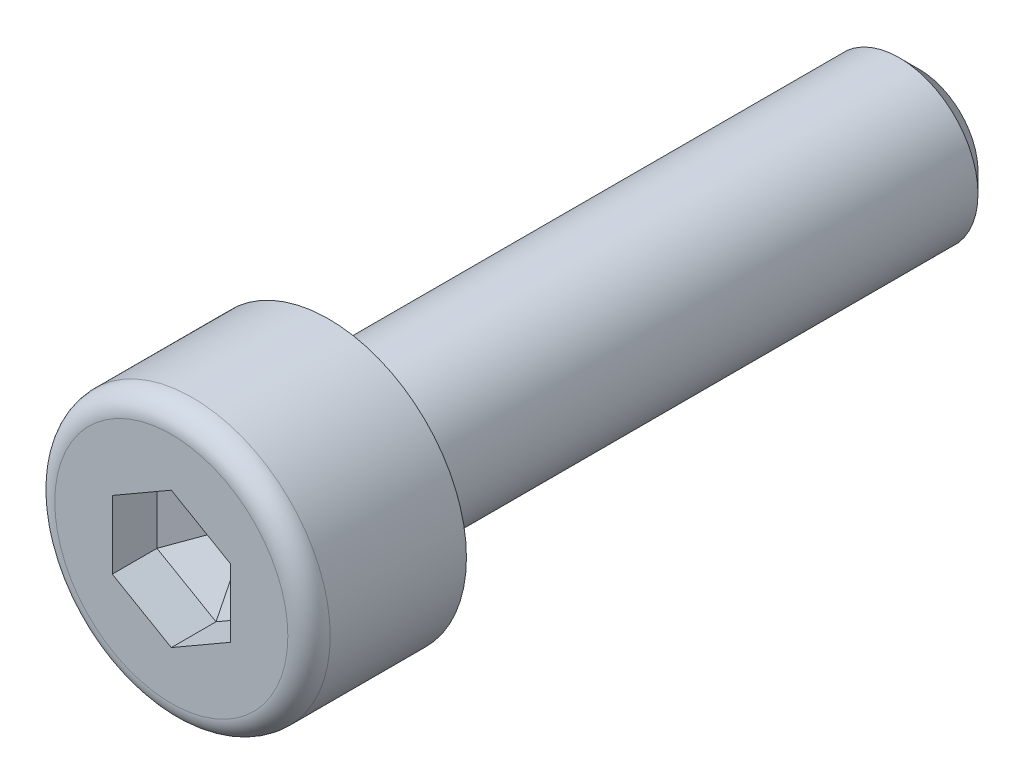
SolidWorks part; units mm, degrees
material "普通碳钢"
ref_plane "前视基准面" through (0, 0, 0) normal (0, 0, 1) x (1, 0, 0)
ref_plane "上视基准面" through (0, 0, 0) normal (0, 1, 0) x (1, 0, 0)
ref_plane "右视基准面" through (0, 0, 0) normal (1, 0, 0) x (0, 0, -1)
sketch "草图1" plane through (0, 0, 0) normal (0, 0, 1) x (1, 0, 0)
  circle A0 centre (0, 0) radius 3.5
  dimension "dk" = 7
extrude "凸台-拉伸1" add sketch "草图1" along normal blind 4
ref_axis "基准轴1" through (0, 0, 4) along (0, 0, -1)
sketch "草图2" plane through (0, 0, 4) normal (0, 0, 1) x (1, 0, 0)
  line L1 (1.5, 0.866) -> (0, 1.7321)
  line L2 (0, 1.7321) -> (-1.5, 0.866)
  line L3 (-1.5, 0.866) -> (-1.5, -0.866)
  line L4 (-1.5, -0.866) -> (0, -1.7321)
  line L5 (0, -1.7321) -> (1.5, -0.866)
  line L6 (1.5, -0.866) -> (1.5, 0.866)
  circle A0 centre (0, 0) radius 1.5 construction
  dimension "s" = 3
extrude "切除-拉伸1" cut sketch "草图2" against normal blind 2
sketch "草图3" plane through (0, 0, 0) normal (0, 0, -1) x (-1, 0, 0)
  circle A0 centre (0, 0) radius 2
  dimension "d" = 4
extrude "凸台-拉伸2" add sketch "草图3" along normal blind 15
cosmetic thread "装饰螺纹线1" parameters "b"=4.9, "D2"=1.221
chamfer "倒角1" distance 0.5 angle 45 1 edges at (-2, 0, -15)
fillet "圆角1" radius 0.5385 1 edges at (3.5, 0, 4)
chamfer "倒角2" distance 0.8646 angle 60 6 edges at (-1.5, 0, 2) (-0.75, 1.299, 2) (0.75, 1.299, 2) (1.5, 0, 2) (-0.75, -1.299, 2) (0.75, -1.299, 2) first distance on face at (-1.5, 0, 3) first distance on face at (-0.75, 1.299, 3) first distance on face at (0.75, 1.299, 3) first distance on face at (1.5, 0, 3) first distance on face at (-0.75, -1.299, 3) first distance on face at (0.75, -1.299, 3)
fillet "圆角2" radius 0.1 1 edges at (2, 0, 0)
ref_plane "基准面1" through (0, 0, 0) normal (0, 0, -1) x (-1, 0, 0)
equation "\"D1@倒角2\" = \"s@草图2\" / 3.47"
equation "\"D1@圆角1\"= \"dk@草图1\" / 13"
equation "\"D1@倒角1\"= \"d@草图3\" / 8"
equation "\"D1@圆角2\"= \"d@草图3\" / \"d@草图3\" * 0.1"
